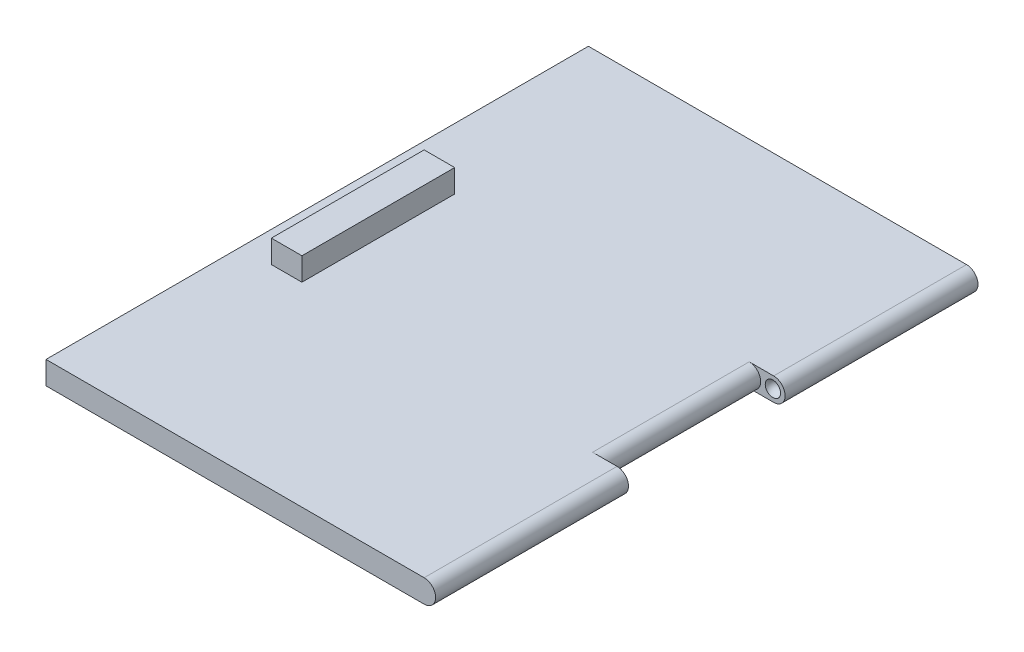
SolidWorks part; units mm, degrees
ref_plane "Front Plane" through (0, 0, 0) normal (0, 0, 1) x (1, 0, 0)
ref_plane "Top Plane" through (0, 0, 0) normal (0, 1, 0) x (1, 0, 0)
ref_plane "Right Plane" through (0, 0, 0) normal (1, 0, 0) x (0, 0, -1)
sketch "Sketch1" plane through (0, 0, 0) normal (0, 1, 0) x (1, 0, 0)
  line L1 (-25.5, 35.5) -> (25.5, 35.5)
  line L2 (-25.5, 35.5) -> (-25.5, -35.5)
  line L3 (-25.5, -35.5) -> (25.5, -35.5)
  line L4 (25.5, 35.5) -> (25.5, -35.5)
  line L5 (-25.5, 35.5) -> (25.5, -35.5) construction
  line L6 (-25.5, -35.5) -> (25.5, 35.5) construction
  point P0 (0, 0)
extrude "Boss-Extrude1" add sketch "Sketch1" along normal blind 3
sketch "Sketch2" plane through (0, 3, 0) normal (0, 1, 0) x (1, 0, 0)
  line L0 (-25.5, 35.5) -> (-25.5, -35.5) construction
  line L1 (-21.5, 10) -> (-17.5, 10)
  line L2 (-21.5, 10) -> (-21.5, -10)
  line L3 (-21.5, -10) -> (-17.5, -10)
  line L4 (-17.5, 10) -> (-17.5, -10)
  line L5 (-21.5, 10) -> (-17.5, -10) construction
  line L6 (-21.5, -10) -> (-17.5, 10) construction
  point P0 (-19.5, 0)
  dimension "D1" = 4
extrude "Boss-Extrude3" add sketch "Sketch2" along normal blind 3
sketch "Sketch4" plane through (0, 3, 0) normal (0, 1, 0) x (1, 0, 0)
  line L0 (25.5, -35.5) -> (25.5, 35.5) construction
  line L1 (22.3, -10.25) -> (25.5, -10.25)
  line L2 (22.3, -10.25) -> (22.3, 10.25)
  line L3 (22.3, 10.25) -> (25.5, 10.25)
  line L4 (25.5, -10.25) -> (25.5, 10.25)
  line L5 (22.3, -10.25) -> (25.5, 10.25) construction
  line L6 (22.3, 10.25) -> (25.5, -10.25) construction
  point P0 (23.9, 0)
extrude "Cut-Extrude1" cut sketch "Sketch4" against normal blind 5
ref_plane "Midsection (Short)" through (0, 0, 0) normal (0, 0, 1) x (1, 0, 0)
sketch "Sketch6" plane through (0, 0, -10.25) normal (0, 0, 1) x (1, 0, 0)
  line L0 (22.9, 1.5) -> (24.9, 1.5)
  arc A0 (24.9, 1.5) -> (22.9, 1.5) centre (23.9, 1.5) cw
revolve "Cut-Revolve1" cut sketch "Sketch6" angle 360 about L0
mirror "Mirror1" about plane through (0, 0, 0) normal (0, 0, 1) of "Cut-Revolve1"
fillet "Fillet1" 2 edges at (25.5, 3, 22.875) (25.5, 0, 22.875) type full round first side face at (11.95, 3, 0) second side face at (11.95, 0, 0) middle face at (25.5, 1.5, 22.875)
fillet "Fillet2" 2 edges at (22.3, 3, 0) (22.3, 0, 0) type full round first side face at (11.575, 3, 0) second side face at (11.575, 0, 0) middle face at (22.3, 1.5, 0)
fillet "Fillet3" 2 edges at (25.5, 3, -22.875) (25.5, 0, -22.875) type full round first side face at (11.2, 3, 0) second side face at (11.2, 0, 0) middle face at (25.5, 1.5, -22.875)
